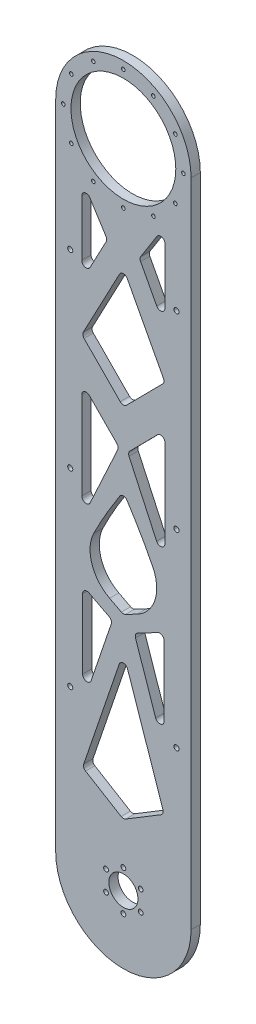
SolidWorks part; units mm, degrees
material "1060 Alloy"
ref_plane "Front Plane" through (0, 0, 0) normal (0, 0, 1) x (1, 0, 0)
ref_plane "Top Plane" through (0, 0, 0) normal (0, 1, 0) x (1, 0, 0)
ref_plane "Right Plane" through (0, 0, 0) normal (1, 0, 0) x (0, 0, -1)
sketch "Sketch2" plane through (0, 0, 0) normal (0, 0, 1) x (1, 0, 0)
  line L0 (0, 0) -> (0, 500) construction
  line L1 (-46.5, 0) -> (-46.5, 500)
  line L2 (46.5, 0) -> (46.5, 500)
  arc A0 (-46.5, 0) -> (46.5, 0) centre (0, 0) ccw
  arc A1 (46.5, 500) -> (-46.5, 500) centre (0, 500) ccw
  circle A2 centre (0, 500) radius 37.25 construction
  circle A3 centre (0, 0) radius 10
  circle A4 centre (0, 13.75) radius 1.65
  circle A5 centre (0, 0) radius 13.75 construction
  circle A6 centre (11.9078, 6.875) radius 1.65
  circle A7 centre (11.9078, -6.875) radius 1.65
  circle A8 centre (0, -13.75) radius 1.65
  circle A9 centre (-11.9078, -6.875) radius 1.65
  circle A10 centre (-11.9078, 6.875) radius 1.65
  point P3 (0, 250)
  point P27 (0, 0)
  dimension "D2" = 74.5
  dimension "D4" = 20
  dimension "D5" = 3.3
  dimension "D6" = 27.5
  dimension "D3" = 46.5
  dimension "D1" = 500
  dimension "D7" = 6
extrude "Boss-Extrude1" add sketch "Sketch2" along normal blind 6.35
sketch "Sketch4" plane through (0, 0, 6.35) normal (0, 0, 1) x (1, 0, 0)
  line L0 (0, 500) -> (0, 999.1647) construction
  line L29 (46.5, 500) -> (-46.5, 500) construction
  line L31 (28.0053, 59.376) -> (0, 42.4117)
  line L32 (0, 141.6934) -> (28.0053, 59.376)
  line L33 (-28.0053, 59.376) -> (0, 141.6934)
  line L34 (0, 42.4117) -> (-28.0053, 59.376)
  line L35 (-7.5, 156.9059) -> (-28.0053, 96.6336)
  line L36 (-28.0053, 167.5829) -> (-7.5, 156.9059)
  line L37 (-28.0053, 96.6336) -> (-28.0053, 167.5829)
  line L38 (28.0053, 167.5829) -> (7.5, 156.9059)
  line L39 (28.0053, 96.6336) -> (28.0053, 167.5829)
  line L40 (7.5, 156.9059) -> (28.0053, 96.6336)
  line L41 (0, 164.2751) -> (28.5505, 179.1412)
  line L42 (0, 164.2751) -> (-28.5505, 179.1412)
  line L43 (28.5505, 259.5868) -> (3, 314.9383)
  line L44 (28.5505, 340.7931) -> (28.5505, 259.5868)
  line L45 (3, 314.9383) -> (28.5505, 340.7931)
  line L46 (-3, 314.9383) -> (-28.5505, 340.7931)
  line L47 (-28.5505, 259.5868) -> (-3, 314.9383)
  line L48 (-28.5505, 340.7931) -> (-28.5505, 259.5868)
  line L49 (0, 423.1428) -> (-28.5505, 369.2462)
  line L50 (-28.5505, 369.2462) -> (0, 340.3557)
  line L51 (0, 340.3557) -> (28.5505, 369.2462)
  line L52 (0, 423.1428) -> (28.5505, 369.2462)
  line L53 (-28.5505, 462.0952) -> (-28.5505, 401.2902)
  line L54 (-11, 434.4215) -> (-28.5505, 462.0952)
  line L55 (-28.5505, 401.2902) -> (-11, 434.4215)
  line L56 (28.5505, 401.2902) -> (11, 434.4215)
  line L57 (28.5505, 462.0952) -> (28.5505, 401.2902)
  line L58 (11, 434.4215) -> (28.5505, 462.0952)
  arc A0 (46.5, 500) -> (-46.5, 500) centre (0, 500) ccw construction
  arc A1 (46.5, 500) -> (-46.5, 500) centre (0, 500) ccw construction
  spline S2 degree 3 poles (28.5505, 179.1412) (45.3203, 216.9857) (19.4301, 259.7903) (0, 290.0258) knots 0 0 0 0 1 1 1 1
  spline S3 degree 3 poles (-28.5505, 179.1412) (-45.3203, 216.9857) (-19.4301, 259.7903) (0, 290.0258) knots 0 0 0 0 1 1 1 1
extrude "Cut-Extrude1" cut sketch "Sketch4" against normal blind 10
fillet "Fillet3" radius 3 30 edges at (-11, 434.4215, 3.175) (-28.5505, 401.2902, 3.175) (28.5505, 401.2902, 3.175) (11, 434.4215, 3.175) (28.5505, 462.0952, 3.175) (-28.5505, 462.0952, 3.175) (0, 423.1428, 3.175) (-28.5505, 369.2462, 3.175) (28.5505, 369.2462, 3.175) (0, 340.3557, 3.175) (28.5505, 340.7931, 3.175) (-28.5505, 340.7931, 3.175) (-3, 314.9383, 3.175) (3, 314.9383, 3.175) (28.5505, 259.5868, 3.175) (-28.5505, 259.5868, 3.175) (28.5505, 179.1412, 3.175) (0, 290.0258, 3.175) (-28.5505, 179.1412, 3.175) (0, 164.2751, 3.175) (-28.0053, 96.6336, 3.175) (28.0053, 96.6336, 3.175) (7.5, 156.9059, 3.175) (-28.0053, 167.5829, 3.175) (28.0053, 167.5829, 3.175) (0, 141.6934, 3.175) (28.0053, 59.376, 3.175) (-28.0053, 59.376, 3.175) (0, 42.4117, 3.175) (-7.5, 156.9059, 3.175)
sketch "Sketch5" plane through (0, 0, 6.35) normal (0, 0, 1) x (1, 0, 0)
  line L0 (0, -46.5) -> (108.8395, -46.5) construction
  line L1 (46.5, 100) -> (-46.5, 100) construction
  line L2 (46.5, 0) -> (46.5, 500) construction
  line L3 (-46.5, 500) -> (-46.5, 0) construction
  line L4 (-46.5, 106.35) -> (46.5, 106.35) construction
  line L5 (36.5, 106.35) -> (36.5, 100) construction
  line L6 (0, 106.35) -> (0, 100) construction
  line L7 (-46.5, 256.35) -> (46.5, 256.35) construction
  line L8 (-46.5, 181.35) -> (46.5, 181.35) construction
  line L9 (-46.5, 337.7) -> (46.5, 337.7) construction
  arc A1 (-46.5, 0) -> (46.5, 0) centre (0, 0) ccw construction
  circle A2 centre (36.5, 103.175) radius 1.75
  circle A3 centre (-36.5, 103.175) radius 1.75
  circle A4 centre (36.5, 259.525) radius 1.75
  circle A5 centre (-36.5, 259.525) radius 1.75
  circle A6 centre (36.5, 415.875) radius 1.75
  circle A7 centre (-36.5, 415.875) radius 1.75
  point P18 (36.5, 103.175)
  dimension "D2" = 3.5
  dimension "D1" = 146.5
  dimension "D3" = 10
  dimension "D4" = 6.35
  dimension "D5" = 150
  dimension "D6" = 81.35
  dimension "D7" = 81.35
extrude "Cut-Extrude2" cut sketch "Sketch5" against normal through all
sketch "Sketch6" plane through (0, 0, 6.35) normal (0, 0, 1) x (1, 0, 0)
  circle A0 centre (0, 500) radius 26.5
  arc A1 (46.5, 500) -> (-46.5, 500) centre (0, 500) ccw construction
  arc A2 (46.5, 500) -> (-46.5, 500) centre (0, 500) ccw construction
  dimension "D1" = 20
extrude "Cut-Extrude3" cut sketch "Sketch6" against normal blind 10
sketch "Sketch7" plane through (0, 0, 6.35) normal (0, 0, 1) x (1, 0, 0)
  line L1 (40.0163, 523.6842) -> (44.1104, 529.9682) construction
  line L2 (23.6842, 540.0163) -> (29.9682, 544.1104) construction
  line L3 (44.1104, 529.9682) -> (29.9682, 544.1104)
  line L4 (0, 500) -> (37.0393, 537.0393) construction
  line L5 (0, 500) -> (0, 546.5) construction
  arc A0 (46.5, 500) -> (-46.5, 500) centre (0, 500) ccw construction
  arc A1 (29.9682, 544.1104) -> (16.4747, 543.4837) centre (22.4977, 559.381) cw
  arc A2 (44.1104, 529.9682) -> (43.4837, 516.4747) centre (59.381, 522.4977) ccw
  arc A3 (16.4747, 543.4837) -> (43.4837, 516.4747) centre (0, 500) cw
  dimension "D3" = 17
  dimension "D5" = 17
  dimension "D1" = 20
  dimension "D2" = 7.5
  dimension "D4" = 8
  dimension "D6" = 8
  dimension "D7" = 45
extrude "Boss-Extrude2" add sketch "Sketch7" against normal up to surface (6.35 mm away) up to face at (26.5, 500, 0)
sketch "Sketch8" plane through (287.0393, 287.0393, 0) normal (0.7071, 0.7071, 0) x (0, 0, -1)
  line L0 (0, 363.5534) -> (-6.35, 363.5534) construction
  line L1 (0, 343.5534) -> (-6.35, 343.5534) construction
  line L2 (-6.35, 343.5534) -> (-6.35, 363.5534) construction
  point P0 (-3.175, 359.5534)
  point P1 (-3.175, 347.5534)
  dimension "D1" = 4
  dimension "D2" = 4
  dimension "D3" = 3.175
hole_wizard "Tap Drill for M3x0.5 Tap1" positions "Sketch8" profile "Sketch9" hole size "M3x0.5" standard "ANSI Metric"
sketch "Sketch9" plane through (32.7967, 541.282, 3.175) normal (0, 0, 1) x (-0.7071, 0.7071, 0)
  line L0 (0, 0) -> (0, 5.7511)
  line L1 (0, 5.7511) -> (1.25, 5)
  line L2 (1.25, 5) -> (1.25, 0)
  line L5 (1.25, 0) -> (0, 0)
  line L10 (0, 5.7511) -> (-1.25, 5) construction
  line L11 (0, -6.35) -> (0, 107.95) construction
  dimension "Hole Dia." = 2.5
  dimension "Hole Depth" = 5
  dimension "Drill Angle" = 118
pattern_circular "CirPattern2" count 2 every 90 about axis through (0, 500, -3.65) along (0, 0, 1) of "Boss-Extrude2", "Tap Drill for M3x0.5 Tap1"
sketch "Sketch10" plane through (0, 0, 6.35) normal (0, 0, 1) x (1, 0, 0)
  line L0 (-43.4837, 516.4747) -> (-63.4837, 516.4747)
  line L1 (43.4837, 516.4747) -> (63.4837, 516.4747)
  arc A0 (43.4837, 516.4747) -> (-43.4837, 516.4747) centre (0, 500) ccw
  arc A1 (46.5, 500) -> (43.4837, 516.4747) centre (0, 500) ccw construction
  arc A2 (-63.4837, 516.4747) -> (63.4837, 516.4747) centre (0, 500) cw
  dimension "D1" = 19.0866
  dimension "D2" = 20
extrude "Cut-Extrude4" cut sketch "Sketch10" against normal through all
sketch "Sketch11" plane through (0, 0, 6.35) normal (0, 0, 1) x (1, 0, 0)
  circle A0 centre (0, 500) radius 36
  circle A1 centre (0, 500) radius 26.5 construction
  dimension "D1" = 72
extrude "Cut-Extrude5" cut sketch "Sketch11" against normal through all
sketch "Sketch12" plane through (0, 0, 6.35) normal (0, 0, 1) x (1, 0, 0)
  line L0 (0, 536) -> (0, 546.5) construction
  circle A0 centre (0, 500) radius 41.25 construction
  circle A1 centre (0, 500) radius 36 construction
  arc A2 (46.5, 500) -> (-46.5, 500) centre (0, 500) ccw construction
  circle A3 centre (0, 541.25) radius 1.25
  circle A4 centre (20.625, 535.7235) radius 1.25
  circle A5 centre (35.7235, 520.625) radius 1.25
  circle A6 centre (41.25, 500) radius 1.25
  circle A7 centre (35.7235, 479.375) radius 1.25
  circle A8 centre (20.625, 464.2765) radius 1.25
  circle A9 centre (0, 458.75) radius 1.25
  circle A10 centre (-20.625, 464.2765) radius 1.25
  circle A11 centre (-35.7235, 479.375) radius 1.25
  circle A12 centre (-41.25, 500) radius 1.25
  circle A13 centre (-35.7235, 520.625) radius 1.25
  circle A14 centre (-20.625, 535.7235) radius 1.25
  point P9 (0, 541.25)
  point P36 (0, 500)
  dimension "D1" = 2.5
  dimension "D2" = 12
extrude "Cut-Extrude6" cut sketch "Sketch12" against normal through all both and the other way through all
sketch "Sketch13" plane through (0, 0, 0) normal (0, 0, -1) x (-1, 0, 0)
  line L0 (28.984, 180.1429) -> (28.984, 234.0954) construction
  line L1 (-28.984, 180.1429) -> (-28.984, 234.0954) construction
  line L2 (46.5, 234.0954) -> (-46.5, 234.0954)
  line L3 (46.5, 500) -> (46.5, 0) construction
  line L4 (-46.5, 0) -> (-46.5, 500) construction
  line L5 (46.5, 180.1429) -> (-46.5, 180.1429)
  line L6 (-46.5, 234.0954) -> (-46.5, 180.1429)
  line L7 (46.5, 234.0954) -> (46.5, 180.1429)
  spline S0 degree 3 poles (2.5314, 286.068) (21.3968, 256.4039) (44.1773, 216.1126) (28.984, 180.1429) knots 0.042883 0.042883 0.042883 0.042883 0.991187 0.991187 0.991187 0.991187 construction
  spline S1 degree 3 poles (-28.984, 180.1429) (-44.1773, 216.1126) (-21.3968, 256.4039) (-2.5314, 286.068) knots 0.008813 0.008813 0.008813 0.008813 0.957117 0.957117 0.957117 0.957117 construction
extrude "Cut-Extrude7" cut sketch "Sketch13" against normal through all
move or copy body "Body-Move/Copy1" bodies to move or copy 111 copy no translate (0, -52.7177, 0) parameters "D1"=0, "D2"=52.7177, "D3"=0
sketch "Sketch14" plane through (0, 180.1429, 0) normal (0, 1, 0) x (1, 0, 0)
  line L0 (-28.984, 0) -> (-46.5, 0) construction
  line L1 (-46.5, 0) -> (-46.5, -6.35) construction
  line L2 (-46.5, -6.35) -> (-28.984, -6.35) construction
  line L3 (-28.984, -6.35) -> (-28.984, 0) construction
  line L4 (28.984, -6.35) -> (46.5, -6.35) construction
  line L5 (46.5, -6.35) -> (46.5, 0) construction
  line L6 (46.5, 0) -> (28.984, 0) construction
  line L7 (28.984, 0) -> (28.984, -6.35) construction
  line L8 (-28.984, 0) -> (-46.5, 0)
  line L9 (-46.5, 0) -> (-46.5, -6.35)
  line L10 (-46.5, -6.35) -> (-28.984, -6.35)
  line L11 (-28.984, -6.35) -> (-28.984, 0)
  line L12 (28.984, -6.35) -> (46.5, -6.35)
  line L13 (46.5, -6.35) -> (46.5, 0)
  line L14 (46.5, 0) -> (28.984, 0)
  line L15 (28.984, 0) -> (28.984, -6.35)
extrude "Boss-Extrude3" add sketch "Sketch14" along normal up to surface (1.2348 mm away) up to face at (37.742, 181.3777, 3.175)
sketch "Sketch15" plane through (0, 0, 0) normal (0, 0, -1) x (-1, 0, 0)
  line L0 (-1.3855, 164.9966) -> (-27.606, 178.6494) construction
  line L1 (28.984, 181.3777) -> (28.984, 180.1429)
  line L2 (-28.984, 181.3777) -> (-28.984, 180.1429) construction
  line L3 (-9.4381, 169.1895) -> (-27.606, 178.6494)
  line L4 (-28.984, 181.3777) -> (-28.984, 180.1429)
  line L5 (0, 493.7823) -> (0, -46.5) construction
  line L6 (9.4381, 169.1895) -> (27.606, 178.6494)
  arc A0 (-20.3344, 202.3794) -> (-9.4381, 169.1895) centre (2.1078, 191.3636) ccw
  arc A1 (-28.984, 180.1429) -> (-27.606, 178.6494) centre (-26.2204, 181.3103) ccw construction
  arc A2 (-28.984, 180.1429) -> (-27.606, 178.6494) centre (-26.2204, 181.3103) ccw
  arc A3 (46.5, 447.2823) -> (-46.5, 447.2823) centre (0, 447.2823) ccw construction
  arc A4 (-46.5, 0) -> (46.5, 0) centre (0, 0) ccw construction
  arc A5 (28.984, 180.1429) -> (27.606, 178.6494) centre (26.2204, 181.3103) cw
  arc A6 (20.3344, 202.3794) -> (9.4381, 169.1895) centre (-2.1078, 191.3636) cw
  spline S0 degree 3 poles (1953.7087, 263.1445) (-2215.7642, -533.3919) (2154.4506, 1213.369) (-1849.5555, -532.5784) knots -2.670349 -2.670349 -2.670349 -2.670349 4.338748 4.338748 4.338748 4.338748 only from (-28.984, 181.3777) to (-2.5314, 233.3503) construction
  spline S1 degree 3 poles (28.984, 181.3777) (26.6659, 188.5284) (23.6788, 195.566) (20.3344, 202.3794) knots 0.47109 0.47109 0.47109 0.47109 0.656208 0.656208 0.656208 0.656208
  spline S2 degree 3 poles (-28.984, 181.3777) (-26.6659, 188.5284) (-23.6788, 195.566) (-20.3344, 202.3794) knots 0.47109 0.47109 0.47109 0.47109 0.656208 0.656208 0.656208 0.656208
  dimension "D1" = 25
  dimension "D2" = 540.2823
extrude "Boss-Extrude4" add sketch "Sketch15" against normal up to surface (6.35 mm away) up to face at (2.6453, 187.7844, 6.35)
sketch "Sketch16" plane through (0, 0, 0) normal (0, 0, -1) x (-1, 0, 0)
  line L0 (36.5, 103.175) -> (36.5, 363.1573) construction
  line L1 (-36.5, 103.175) -> (-36.5, 363.1573) construction
  circle A0 centre (-36.5, 363.1573) radius 1.75 construction
  circle A1 centre (36.5, 363.1573) radius 1.75 construction
  circle A2 centre (-36.5, 103.175) radius 1.75 construction
  circle A3 centre (36.5, 103.175) radius 1.75 construction
  circle A4 centre (-36.5, 363.1573) radius 1.75 construction
  circle A5 centre (36.5, 363.1573) radius 1.75 construction
  circle A6 centre (-36.5, 103.175) radius 1.75 construction
  circle A7 centre (36.5, 103.175) radius 1.75 construction
  circle A8 centre (36.5, 233.1662) radius 1.75
  circle A9 centre (-36.5, 233.1662) radius 1.75
  point P16 (36.5, 233.1662)
  point P18 (36.5, 233.1662)
extrude "Cut-Extrude8" cut sketch "Sketch16" against normal through all
sketch "Sketch17" plane through (0, 0, 0) normal (0, 0, -1) x (-1, 0, 0)
  circle A0 centre (36.5, 206.8073) radius 1.75 construction
  circle A1 centre (-36.5, 206.8073) radius 1.75 construction
  circle A2 centre (36.5, 206.8073) radius 1.75
  circle A3 centre (-36.5, 206.8073) radius 1.75
extrude "Boss-Extrude5" add sketch "Sketch17" against normal up to surface (6.35 mm away) up to face at (-34.75, 233.1662, 6.35)
equation "\"L1L\"=500"
equation "\"L1Thick\"=6.35"
equation "\"D1@Sketch2\"=\"L1L\""
equation "\"Harm-Drive-Outer\"=74.5"
equation "\"D2@Sketch2\"=\"Harm-Drive-Outer\""
equation "\"D1@Boss-Extrude1\"=\"L1Thick\""
